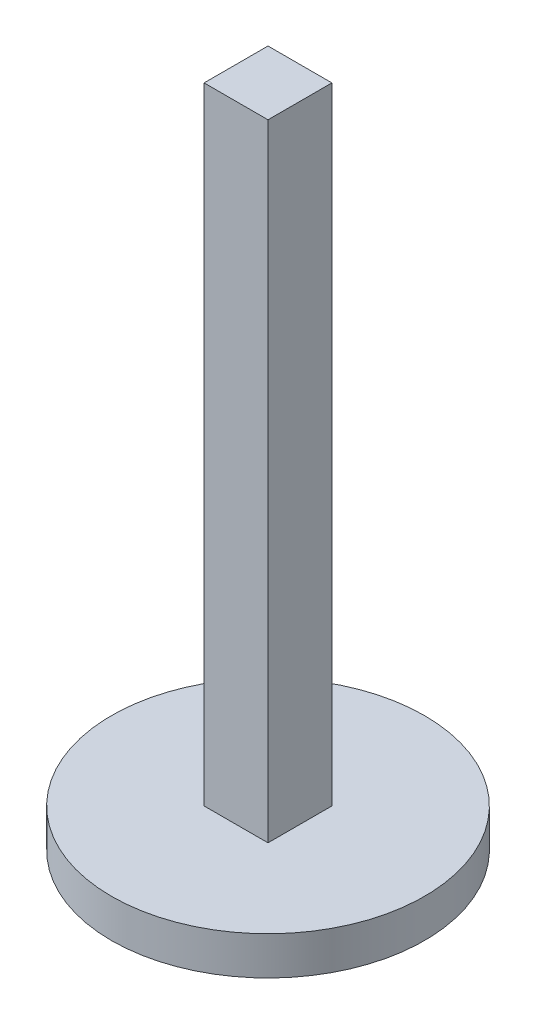
SolidWorks part; units mm, degrees
ref_plane "Front Plane" through (0, 0, 0) normal (0, 0, 1) x (1, 0, 0)
ref_plane "Top Plane" through (0, 0, 0) normal (0, 1, 0) x (1, 0, 0)
ref_plane "Right Plane" through (0, 0, 0) normal (1, 0, 0) x (0, 0, -1)
sketch "Sketch1" plane through (0, 0, 0) normal (0, 1, 0) x (1, 0, 0)
  line L1 (-1.25, -1.25) -> (1.25, -1.25)
  line L2 (-1.25, -1.25) -> (-1.25, 1.25)
  line L3 (-1.25, 1.25) -> (1.25, 1.25)
  line L4 (1.25, -1.25) -> (1.25, 1.25)
  line L5 (-1.25, -1.25) -> (1.25, 1.25) construction
  line L6 (-1.25, 1.25) -> (1.25, -1.25) construction
  circle A0 centre (0, 0) radius 6.125
  dimension "D1" = 12.25
  dimension "D2" = 2.5
  dimension "D3" = 2.5
extrude "Boss-Extrude1" add sketch "Sketch1" along normal blind 1.5
extrude "Boss-Extrude2" add sketch "Sketch1<2>" along normal blind 26 contours L2 L3 L4 L1
sketch "Sketch1<2>" plane through (0, 0, 0) normal (0, 1, 0) x (1, 0, 0) same geometry as "Sketch1"
